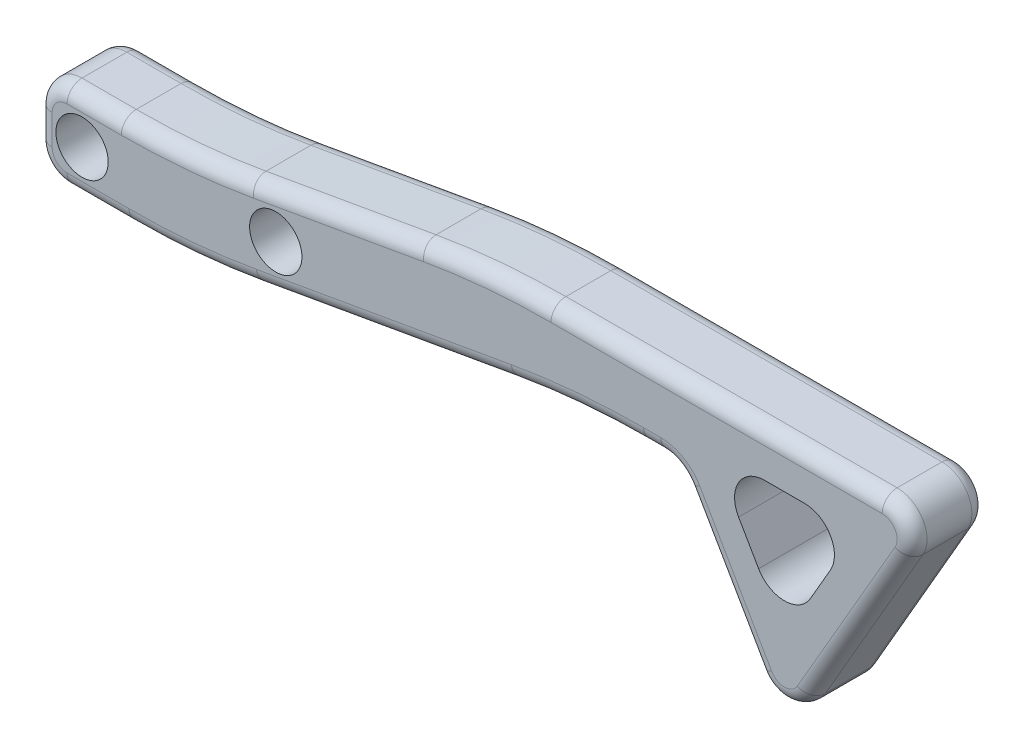
SolidWorks part; units mm, degrees
ref_plane "Front Plane" through (0, 0, 0) normal (0, 0, 1) x (1, 0, 0)
ref_plane "Top Plane" through (0, 0, 0) normal (0, 1, 0) x (1, 0, 0)
ref_plane "Right Plane" through (0, 0, 0) normal (1, 0, 0) x (0, 0, -1)
sketch "Sketch1" plane through (0, 0, 0) normal (0, 0, 1) x (1, 0, 0)
  line L0 (4.3744, 0) -> (26.5359, 0)
  line L1 (28.2679, -3) -> (21.7321, -14.3205)
  line L2 (18.2679, -14.3205) -> (13.4641, -6)
  line L3 (11.7321, -5) -> (10.5706, -5)
  line L4 (1.8882, -5.7596) -> (-15.1671, -8.7669)
  line L5 (-23.8495, -9.5265) -> (-28, -9.5265)
  line L6 (-30, -7.5265) -> (-30, -5.5265)
  line L7 (-28, -3.5265) -> (-24.3744, -3.5265)
  line L8 (-15.692, -2.7669) -> (-4.308, -0.7596)
  line L9 (21.7321, -8.3205) -> (23.0718, -6)
  line L10 (21.3397, -3) -> (18.6603, -3)
  line L11 (16.9282, -6) -> (18.2679, -8.3205)
  arc A0 (-28, -9.5265) -> (-30, -7.5265) centre (-28, -7.5265) cw
  arc A1 (-30, -5.5265) -> (-28, -3.5265) centre (-28, -5.5265) cw
  arc A2 (13.4641, -6) -> (11.7321, -5) centre (11.7321, -7) ccw
  arc A3 (18.6603, -3) -> (16.9282, -6) centre (18.6603, -5) ccw
  arc A4 (23.0718, -6) -> (21.3397, -3) centre (21.3397, -5) ccw
  arc A5 (26.5359, 0) -> (28.2679, -3) centre (26.5359, -2) cw
  arc A6 (21.7321, -8.3205) -> (18.2679, -8.3205) centre (20, -7.3205) cw
  arc A7 (21.7321, -14.3205) -> (18.2679, -14.3205) centre (20, -13.3205) cw
  arc A8 (10.5706, -5) -> (1.8882, -5.7596) centre (10.5706, -55) ccw
  arc A9 (4.3744, 0) -> (-4.308, -0.7596) centre (4.3744, -50) ccw
  arc A10 (-15.1671, -8.7669) -> (-23.8495, -9.5265) centre (-23.8495, 40.4735) cw
  arc A11 (-24.3744, -3.5265) -> (-15.692, -2.7669) centre (-24.3744, 46.4735) ccw
  point P13 (-30, -9.5265)
  point P18 (-30, -3.5265)
  point P27 (30, 0)
  point P32 (20, -17.3205)
  point P37 (0, 0)
  point P42 (-20, -3.5265)
  dimension "D14" = 2
  dimension "D15" = 50
  dimension "D1" = 30
  dimension "D2" = 10
  dimension "D3" = 20
  dimension "D4" = 10
  dimension "D5" = 6
  dimension "D6" = 6
  dimension "D7" = 5
  dimension "D8" = 60
  dimension "D9" = 60
  dimension "D10" = 20
  dimension "D11" = 3
  dimension "D12" = 3
  dimension "D13" = 3
extrude "Boss-Extrude1" add sketch "Sketch1" along normal blind 5
fillet "Fillet1" radius 1 36 edges at (0.0166, -0.1903, 0) (15.4552, 0, 0) (28.2679, -1, 0) (25, -8.6603, 0) (20, -15.3205, 0) (15.866, -10.1603, 0) (12.7321, -5.2679, 0) (11.1513, -5, 0) (6.2129, -5.1903, 0) (-6.6394, -7.2633, 0) (-19.4917, -9.3363, 0) (-25.9248, -9.5265, 0) (-29.4142, -8.9408, 0) (-30, -6.5265, 0) (-29.4142, -4.1123, 0) (-26.1872, -3.5265, 0) (-20.0166, -3.3363, 0) (-10, -1.7633, 5) (0.0166, -0.1903, 5) (15.4552, 0, 5) (28.2679, -1, 5) (25, -8.6603, 5) (20, -15.3205, 5) (15.866, -10.1603, 5) (12.7321, -5.2679, 5) (11.1513, -5, 5) (6.2129, -5.1903, 5) (-6.6394, -7.2633, 5) (-19.4917, -9.3363, 5) (-25.9248, -9.5265, 5) (-29.4142, -8.9408, 5) (-30, -6.5265, 5) (-29.4142, -4.1123, 5) (-26.1872, -3.5265, 5) (-10, -1.7633, 0) (-20.0166, -3.3363, 5)
sketch "Sketch2" plane through (0, 0, 5) normal (0, 0, 1) x (1, 0, 0)
  line L0 (-27, -6.5265) -> (-14.0377, -5.5367) construction
  line L1 (-27, -6.5265) -> (-30, -6.5265) construction
  line L2 (-30, -7.5265) -> (-30, -5.5265) construction
  circle A0 centre (-14.0377, -5.5367) radius 1.75
  circle A1 centre (-27, -6.5265) radius 1.75
  point P4 (-14.0377, -5.5367)
  dimension "D2" = 3.5
  dimension "D1" = 13
  dimension "D3" = 3
extrude "Cut-Extrude1" cut sketch "Sketch2" against normal through all
